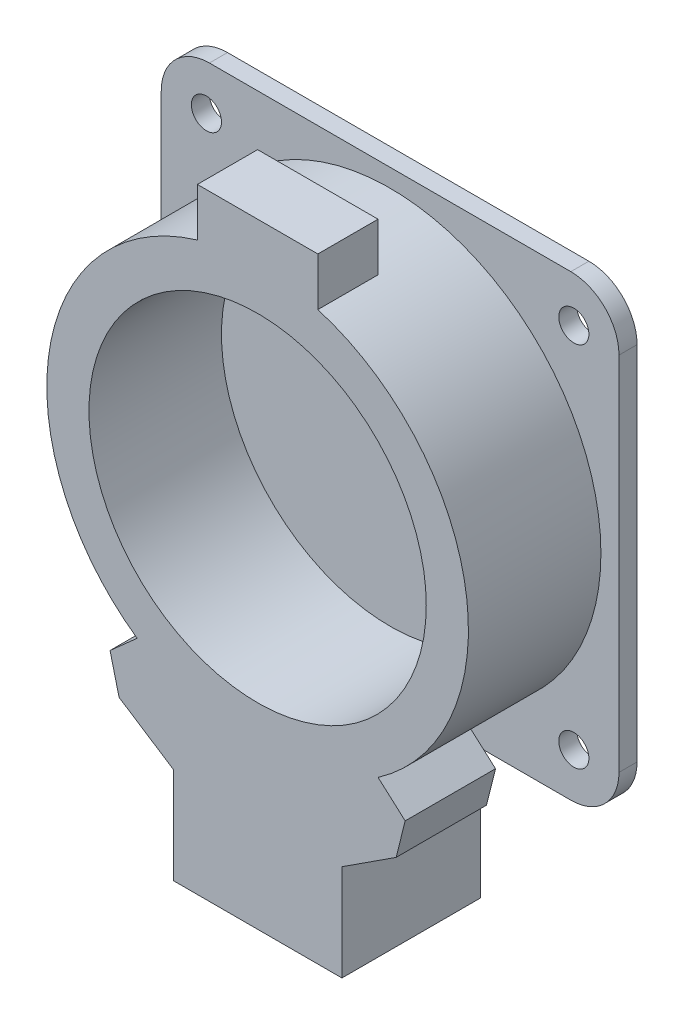
SolidWorks part; units mm, degrees
ref_plane "Front Plane" through (0, 0, 0) normal (0, 0, 1) x (1, 0, 0)
ref_plane "Top Plane" through (0, 0, 0) normal (0, 1, 0) x (1, 0, 0)
ref_plane "Right Plane" through (0, 0, 0) normal (1, 0, 0) x (0, 0, -1)
sketch "Sketch1" plane through (0, 0, 0) normal (0, 0, 1) x (1, 0, 0)
  line L0 (-15.25, 15.25) -> (15.25, 15.25) construction
  line L1 (-15, -19) -> (15, -19)
  line L2 (-19, -15) -> (-19, 15)
  line L3 (-15, 19) -> (15, 19)
  line L4 (19, -15) -> (19, 15)
  line L5 (-19, -19) -> (19, 19) construction
  line L6 (-19, 19) -> (19, -19) construction
  line L7 (15.25, 15.25) -> (15.25, -15.25) construction
  line L8 (15.25, -15.25) -> (-15.25, -15.25) construction
  line L9 (-15.25, -15.25) -> (-15.25, 15.25) construction
  line L10 (0, 0) -> (0, -19) construction
  line L15 (-19, 0) -> (19, 0) construction
  line L16 (-10.5, -13.5) -> (10.5, -13.5)
  line L17 (-10.5, -13.5) -> (-10.5, -19)
  line L18 (-10.5, -19) -> (10.5, -19)
  line L19 (10.5, -13.5) -> (10.5, -19)
  line L20 (-10.5, -13.5) -> (10.5, -19) construction
  line L21 (-10.5, -19) -> (10.5, -13.5) construction
  line L22 (-10, -14.3614) -> (10, -14.3614) construction
  line L27 (-5, 20.7705) -> (5, 20.7705)
  line L28 (-5, 20.7705) -> (-5, 16.7705)
  line L29 (-5, 16.7705) -> (5, 16.7705)
  line L30 (5, 20.7705) -> (5, 16.7705)
  line L31 (-5, 20.7705) -> (5, 16.7705) construction
  line L32 (-5, 16.7705) -> (5, 20.7705) construction
  line L33 (-7, -30.2837) -> (7, -30.2837)
  line L34 (7, -30.2837) -> (7, -22.2837)
  line L35 (-7, -30.2837) -> (-7, -22.2837)
  line L36 (-7, -22.2837) -> (7, -22.2837)
  line L37 (-7, -22.2837) -> (-11.5, -19.3614)
  line L38 (-11.5, -19.3614) -> (11.5, -19.3614) construction
  line L39 (11.5, -19.3614) -> (7, -22.2837)
  line L40 (-11.5, -19.3614) -> (-12.25, -16.3614)
  line L41 (-12.25, -16.3614) -> (12.25, -16.3614) construction
  line L42 (12.25, -16.3614) -> (11.5, -19.3614)
  line L43 (-10, -14.3614) -> (-12.25, -16.3614)
  line L44 (10, -14.3614) -> (12.25, -16.3614)
  line L45 (-7, -22.2837) -> (-7, -19.2837)
  line L46 (-7, -19.2837) -> (7, -19.2837)
  line L47 (7, -19.2837) -> (7, -22.2837)
  arc A6 (-19, -15) -> (-15, -19) centre (-15, -15) ccw
  arc A7 (15, -19) -> (19, -15) centre (15, -15) ccw
  arc A8 (15, 19) -> (19, 15) centre (15, 15) cw
  arc A9 (-15, 19) -> (-19, 15) centre (-15, 15) ccw
  circle A10 centre (-15.25, 15.25) radius 1.25
  circle A11 centre (-15.25, -15.25) radius 1.25
  circle A12 centre (15.25, -15.25) radius 1.25
  circle A13 centre (15.25, 15.25) radius 1.25
  circle A14 centre (-12.25, 0) radius 1.75
  circle A15 centre (12.25, 0) radius 1.75
  circle A16 centre (0, 0) radius 17.5
  circle A17 centre (0, 0) radius 14
  point P0 (0, 0)
  point P22 (0, 18.7705)
  point P24 (0, -16.25)
  point P51 (0, -30.2837)
  point P59 (0, -17.5)
  dimension "D3" = 4
  dimension "D4" = 2.5
  dimension "D8" = 3.5
  dimension "D11" = 35
  dimension "D12" = 28
  dimension "D1" = 38
  dimension "D2" = 38
  dimension "D5" = 3.75
  dimension "D6" = 21
  dimension "D7" = 5.5
  dimension "D9" = 24.5
  dimension "D10" = 6.75
  dimension "D13" = 10
  dimension "D14" = 4
  dimension "D15" = 14
  dimension "D16" = 8
  dimension "D17" = 23
  dimension "D19" = 123
  dimension "D18" = 24.5
  dimension "D20" = 3
  dimension "D21" = 2
  dimension "D22" = 20
  dimension "D23" = 11
extrude "print" add sketch "Sketch1" along normal blind 1.5 contours L3 A8 L4 A7 L1 A6 L2 A9
extrude "print_holes" cut sketch "Sketch1<4>" along normal up to next contours A10 | A13 | A12 | A11
sketch "Sketch1<4>" plane through (0, 0, 0) normal (0, 0, 1) x (1, 0, 0) same geometry as "Sketch1"
extrude "screws" add sketch "Sketch1<5>" against normal blind 3 contours A14 | A15
sketch "Sketch1<5>" plane through (0, 0, 0) normal (0, 0, 1) x (1, 0, 0) same geometry as "Sketch1"
extrude "cableconnector" add sketch "Sketch1<6>" against normal blind 3 contours L19 L18 L17 L16
sketch "Sketch1<6>" plane through (0, 0, 0) normal (0, 0, 1) x (1, 0, 0) same geometry as "Sketch1"
extrude "cam base" add sketch "Sketch1<7>" along normal blind 11 from surface contours A17 L16 L19 A16 L29 L17 | A17 L16 L17 A16 L19 | L29 A16 region at (-16.7682, 2.9972, 0) region at (0, -15.1853, 0) region at (0, 17.0628, 0) starting at face at (-14, -15.25, 1.5)
sketch "Sketch1<7>" plane through (0, 0, 0) normal (0, 0, 1) x (1, 0, 0) same geometry as "Sketch1"
extrude "base clamp" add sketch "Sketch1<8>" against normal blind 5 from surface contours L27 L30 L29 L28 starting at face at (17.5, 0, 12.5)
sketch "Sketch1<8>" plane through (0, 0, 0) normal (0, 0, 1) x (1, 0, 0) same geometry as "Sketch1"
extrude "Boss-Extrude6" add sketch "Sketch1<9>" against normal blind 7.5 from surface contours L17 L43 L40 L1 | A16 L43 L17 L1 L19 L44 | L44 L19 L1 L42 | L42 L1 L40 L37 L36 L39 region at (0, -17.5139, 0) region at (0, -19.2341, 0) region at (-11.1857, -17.1161, 0) region at (11.1857, -17.1161, 0) starting at face at (0, 10.2029, 12.5)
sketch "Sketch1<9>" plane through (0, 0, 0) normal (0, 0, 1) x (1, 0, 0) same geometry as "Sketch1"
extrude "Boss-Extrude7" add sketch "Sketch1<10>" against normal blind 11.5 from surface contours L36 L35 L33 L34 | L47 L46 L45 L36 region at (0, -26.2837, 0) region at (0, -20.7837, 0) starting at face at (0, -7.5057, 12.5)
sketch "Sketch1<10>" plane through (0, 0, 0) normal (0, 0, 1) x (1, 0, 0) same geometry as "Sketch1"
equation "\"D5@Sketch1\"=2.5+0.5*\"D4@Sketch1\""
equation "\"D9@Sketch1\"=21+\"D8@Sketch1\""
equation "\"D10@Sketch1\"=(\"D1@Sketch1\"-\"D9@Sketch1\")/2"
